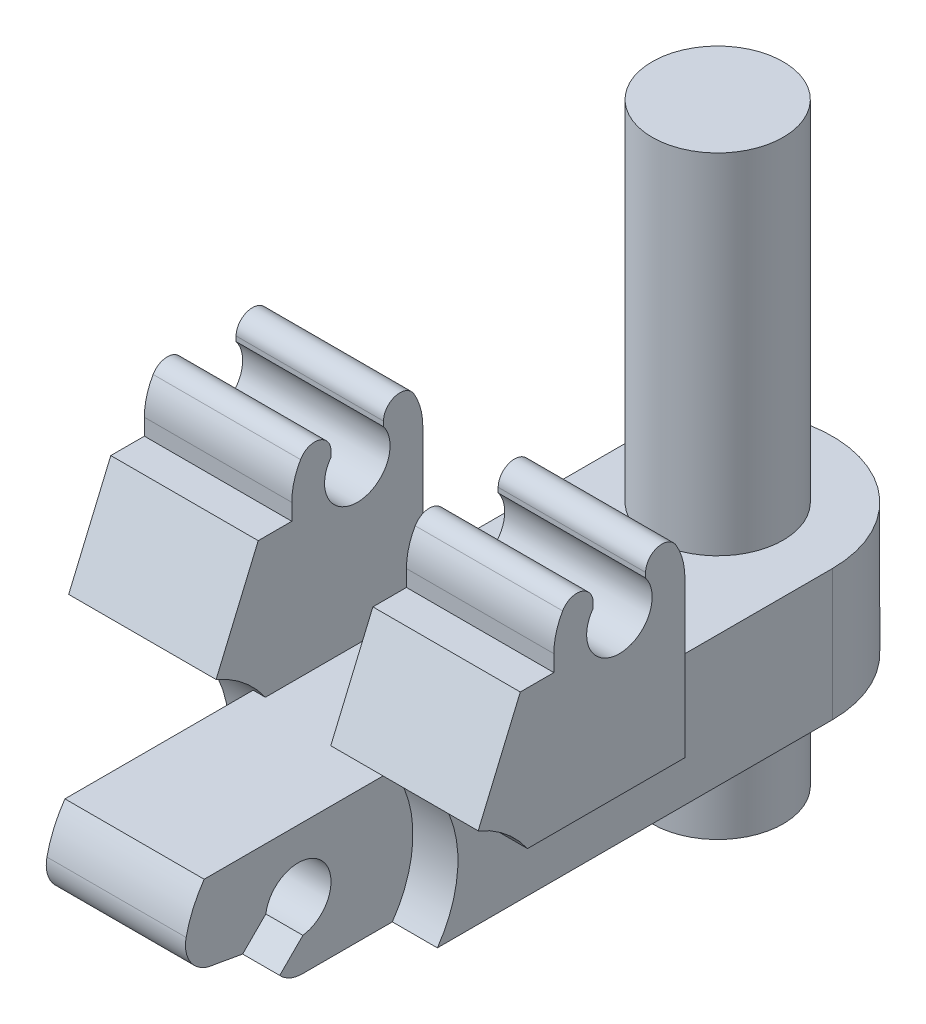
SolidWorks part; units mm, degrees
ref_plane "Front Plane" through (0, 0, 0) normal (0, 0, 1) x (1, 0, 0)
ref_plane "Top Plane" through (0, 0, 0) normal (0, 1, 0) x (1, 0, 0)
ref_plane "Right Plane" through (0, 0, 0) normal (1, 0, 0) x (0, 0, -1)
sketch "Sketch3" plane through (0, 0, 0) normal (1, 0, 0) x (0, 0, -1)
  line L0 (0.2828, -1.9799) -> (-1.9799, 0.2828)
  line L1 (0.2828, -1.9799) -> (-1.1314, -3.3941)
  line L2 (-1.1314, -3.3941) -> (-0.8188, -5.1668)
  line L3 (-0.8188, -5.1668) -> (-2.2728, -6.6208)
  line L4 (-1.9799, 0.2828) -> (-3.3941, -1.1314)
  line L5 (-3.3941, -1.1314) -> (-5.1668, -0.8188)
  line L6 (-5.1668, -0.8188) -> (-6.6208, -2.2728)
  line L7 (-0.8485, -0.8485) -> (0, 0) construction
  line L8 (0, 0) -> (-2, 0) construction
  line L9 (-1.9799, 0.2828) -> (-5.1668, -0.8188) construction
  line L10 (-0.8188, -5.1668) -> (0.2828, -1.9799) construction
  circle A0 centre (0, 0) radius 2
  circle A1 centre (0, 0) radius 6 construction
  circle A2 centre (0, 0) radius 6.5 construction
  circle A3 centre (0, 0) radius 7
  dimension "D1" = 4
  dimension "D2" = 12
  dimension "D3" = 5
  dimension "D4" = 0.5
  dimension "D5" = 2
  dimension "D7" = 3.2
  dimension "D6" = 1.8
  dimension "D8" = 45
  dimension "D9" = 125
extrude "Boss-Extrude1" add sketch "Sketch3" along normal mid plane 8.5 contours A3 L6 L5 L4 A0 L1 L2 L3 | A3 region at (0, -1.4401, -1.6605)
sketch "Sketch5" plane through (0, 0, 0) normal (1, 0, 0) x (0, 0, -1)
  line L0 (0, 7) -> (29.856, 7)
  line L1 (29.856, 7) -> (29.856, -7)
  line L2 (29.856, -7) -> (0, -7)
  arc A0 (-2.2728, -6.6208) -> (-6.6208, -2.2728) centre (0, 0) ccw construction
  arc A1 (0, -7) -> (0, 7) centre (0, 0) ccw
  dimension "D1" = 29.856
extrude "Boss-Extrude2" add sketch "Sketch5" along normal mid plane 14
sketch "Sketch6" plane through (0, 7, 0) normal (0, 1, 0) x (1, 0, 0)
  line L0 (7, 29.856) -> (-7, 29.856) construction
  circle A0 centre (0, 29.856) radius 7
extrude "Boss-Extrude3" add sketch "Sketch6" against normal up to surface (14 mm away) up to face at (0, -7, -9.952)
sketch "Sketch7" plane through (0, 0, 0) normal (0, 1, 0) x (1, 0, 0)
  circle A0 centre (0, 29.856) radius 4
  dimension "D1" = 8
extrude "Boss-Extrude4" add sketch "Sketch7" along normal blind 25.3 and the other way blind 11
sketch "Sketch8" plane through (0, 7, 0) normal (0, 1, 0) x (1, 0, 0)
  line L0 (4.25, -7) -> (4.25, 0) construction
  line L1 (-4.25, 0) -> (-4.25, -7) construction
  line L3 (7, 0) -> (7, 29.856) construction
  line L4 (-7, 29.856) -> (-7, 0) construction
  line L5 (-7, 0) -> (-4.25, 0) construction
  line L6 (4.25, 0) -> (7, 0) construction
  line L7 (4.25, -7) -> (4.25, 0)
  line L8 (-4.25, 0) -> (-4.25, -7)
  line L9 (-4.25, -7) -> (4.25, -7)
  line L10 (7, 0) -> (7, 29.856)
  line L11 (-7, 29.856) -> (-7, 0)
  line L12 (-7, 0) -> (-4.25, 0)
  line L13 (4.25, 0) -> (7, 0)
  arc A0 (7, 29.856) -> (-7, 29.856) centre (0, 29.856) ccw construction
  arc A1 (7, 29.856) -> (-7, 29.856) centre (0, 29.856) ccw
  circle M9 centre (0, 29.856) radius 4
  line M10 (7, 0) -> (7, 29.856)
  arc M11 (7, 29.856) -> (-7, 29.856) centre (0, 29.856) ccw
  line M12 (-7, 29.856) -> (-7, 0)
  line M13 (-7, 0) -> (-4.25, 0)
  line M14 (-4.25, 0) -> (4.25, 0)
  line M15 (4.25, 0) -> (7, 0)
extrude "Cut-Extrude2" cut sketch "Sketch8" against normal offset from surface (3 mm away) 4 contours M15 M10 M11 M12 M13 M14 M9 | L8 L9 L7 M14 region at (0, 7, 3.5) region at (0, 7, -16.3386) up to plane "Top Plane"
sketch "Sketch9" plane through (0, -7, 0) normal (0, -1, 0) x (1, 0, 0)
  line L7 (4.25, 0) -> (4.25, 7)
  line L8 (7, 0) -> (4.25, 0)
  line L9 (7, -29.856) -> (7, 0)
  line L10 (-7, 0) -> (-7, -29.856)
  line L11 (-4.25, 0) -> (-7, 0)
  line L12 (-4.25, 7) -> (-4.25, 0)
  line L13 (4.25, 7) -> (-4.25, 7)
  line L14 (4.25, 0) -> (4.25, 7)
  line L15 (7, 0) -> (4.25, 0)
  line L16 (7, -29.856) -> (7, 0)
  line L17 (-7, 0) -> (-7, -29.856)
  line L18 (-4.25, 0) -> (-7, 0)
  line L19 (-4.25, 7) -> (-4.25, 0)
  line L20 (4.25, 7) -> (-4.25, 7)
  arc A1 (-7, -29.856) -> (7, -29.856) centre (0, -29.856) ccw
  arc A2 (-7, -29.856) -> (7, -29.856) centre (0, -29.856) ccw
  circle M9 centre (0, -29.856) radius 4
  line M10 (-7, 0) -> (-7, -29.856)
  arc M11 (-7, -29.856) -> (7, -29.856) centre (0, -29.856) ccw
  line M12 (7, -29.856) -> (7, 0)
  line M13 (7, 0) -> (4.25, 0)
  line M14 (4.25, 0) -> (-4.25, 0)
  line M15 (-4.25, 0) -> (-7, 0)
  dimension "D1" = 0
extrude "Cut-Extrude4" cut sketch "Sketch9" against normal offset from surface (3 mm away) 4 contours M15 M10 M11 M12 M13 M14 M9 | L14 L20 L19 M14 region at (0, -7, 3.5) region at (0, -7, -16.3386) up to plane "Top Plane"
sketch "Sketch10" plane through (0, 0, 0) normal (1, 0, 0) x (0, 0, -1)
  line L3 (5.7446, -4) -> (29.856, -4)
  line L4 (29.856, -4) -> (29.856, 4)
  line L5 (29.856, 4) -> (5.7446, 4)
  line L10 (7.356, 12.5) -> (7.356, 17.5) construction
  line L11 (7.356, 17.5) -> (15.356, 17.5) construction
  line L12 (15.356, 17.5) -> (15.356, 4) construction
  line L13 (5.3059, 12.5) -> (7.356, 12.5)
  line L14 (0, 0) -> (2.7351, 6.4435) construction
  line L15 (2.7351, 6.4435) -> (5.3059, 12.5)
  line L16 (29.856, 4) -> (5.7446, 4) construction
  line L17 (15.356, 4) -> (5.7446, 4)
  line L18 (7.356, 13.5) -> (15.356, 13.5) construction
  line L19 (29.856, 25.3) -> (29.856, 4) construction
  line L20 (33.856, 25.3) -> (25.856, 25.3) construction
  line L21 (9.756, 14.7) -> (12.956, 14.7) construction
  line L22 (12.956, 14.7) -> (12.956, 17.1661)
  line L23 (9.756, 17.1661) -> (9.756, 14.7)
  line L24 (7.356, 13.5) -> (7.356, 12.5)
  line L25 (15.356, 13.5) -> (15.356, 4)
  arc A0 (9.756, 14.7) -> (12.956, 14.7) centre (11.356, 13.5) ccw
  arc A1 (5.7446, -4) -> (5.7446, 4) centre (0, 0) ccw
  arc A2 (5.7446, 4) -> (2.7351, 6.4435) centre (0, 0) ccw
  arc A3 (15.356, 13.5) -> (12.956, 17.1661) centre (11.356, 13.5) ccw
  arc A4 (9.756, 17.1661) -> (7.356, 13.5) centre (11.356, 13.5) ccw
  point P16 (10.9199, 12.6116)
  dimension "D8" = 4
  dimension "D9" = 2
  dimension "D10" = 3.2
  dimension "D2" = 67
  dimension "D3" = 14.5
  dimension "D4" = 13.5
  dimension "D5" = 5
  dimension "D7" = 5
  dimension "D1" = 0
extrude "Boss-Extrude5" add sketch "Sketch10" along normal mid plane 25
ref_plane "Plane1" through (6, 0, 0) normal (1, 0, 0) x (0, 0, -1)
ref_plane "Plane2" through (-6, 0, 0) normal (1, 0, 0) x (0, 0, -1)
sketch "Sketch13" plane through (-6, 0, 0) normal (1, 0, 0) x (0, 0, -1)
  line L0 (0, 5) -> (33.856, 5)
  line L1 (33.856, 4) -> (33.856, 25.3) construction
  circle A0 centre (0, 0) radius 5 construction
  point P5 (33.856, 5)
  dimension "D1" = 10
ref_plane "Plane3" through (0, 0, 0) normal (0, 0, 1) x (1, 0, 0)
sketch "Sketch14" plane through (0, 0, 0) normal (0, 0, 1) x (1, 0, 0)
  line L0 (-6.5303, 5.5303) -> (-8.0607, 4)
  line L1 (-7, 4) -> (-12.5, 4) construction
  line L2 (-5.4697, 4.4697) -> (-7, 2.9393)
  line L3 (-7, 4) -> (-7, -4) construction
  line L4 (-6.5303, 5.5303) -> (-5.4697, 4.4697) construction
  line L5 (-8.0607, 4) -> (-7, 4)
  line L6 (-7, 4) -> (-7, 2.9393)
  arc A0 (-5.4697, 4.4697) -> (-6.5303, 5.5303) centre (-6, 5) ccw
  point P14 (-6, 5)
  dimension "D1" = 1.5
  dimension "D2" = 45
sweep "Cut-Sweep1" cut profiles "Sketch14" path "Sketch13"
ref_plane "Plane4" through (0, 0, -33.856) normal (0, 0, -1) x (-1, 0, 0)
ref_plane "Plane5" through (-4, 0, 0) normal (-1, 0, 0) x (0, 0, 1)
sketch "Sketch18" plane through (0, 0, -33.856) normal (0, 0, -1) x (-1, 0, 0)
  line L0 (0, 25.3) -> (0, 18.1) construction
  line L1 (4, 25.3) -> (-4, 25.3) construction
  circle A0 centre (0, 18.1) radius 1.9
  dimension "D2" = 3.8
  dimension "D1" = 7.2
extrude "Cut-Extrude5" cut sketch "Sketch18" against normal blind 1
sketch "Sketch19" plane through (-4, 0, 0) normal (-1, 0, 0) x (0, 0, 1)
  line L0 (-29.856, 25.3) -> (-29.856, 18.1) construction
  line L1 (-25.856, 25.3) -> (-33.856, 25.3) construction
  circle A0 centre (-29.856, 18.1) radius 2
  dimension "D2" = 4
  dimension "D1" = 7.2
extrude "Cut-Extrude6" cut sketch "Sketch19" against normal blind 1
sketch "Sketch20" plane through (0, 25.3, 0) normal (0, 1, 0) x (1, 0, 0)
  line L0 (0, 25.856) -> (0, 0) construction
  line L2 (-3.5, -15.356) -> (3.5, -15.356)
  line L3 (-3.5, -15.356) -> (-3.5, 15.356)
  line L4 (-3.5, 15.356) -> (3.5, 15.356)
  line L5 (3.5, -15.356) -> (3.5, 15.356)
  line L6 (-3.5, -15.356) -> (3.5, 15.356) construction
  line L7 (-3.5, 15.356) -> (3.5, -15.356) construction
  line L8 (-5.9393, 15.356) -> (7, 15.356) construction
  circle A0 centre (0, 29.856) radius 4 construction
  circle A1 centre (0, 29.856) radius 4 construction
  point P11 (-3.5, 9.756)
  point P12 (-3.5, 15.356)
  point P14 (0, 0)
  point P15 (0, 0)
  dimension "D1" = 7
extrude "Cut-Extrude7" cut sketch "Sketch20" against normal up to surface (21.3 mm away) up to face at (0, 4, 0)
fillet "Fillet1" radius 1.9 2 edges at (0, -2.2728, 6.6208) (0, -4, 1.0245)
fillet "Fillet2" radius 1 4 edges at (-8, 17.1661, -12.956) (-8, 17.1661, -9.756) (8, 17.1661, -9.756) (8, 17.1661, -12.956)
